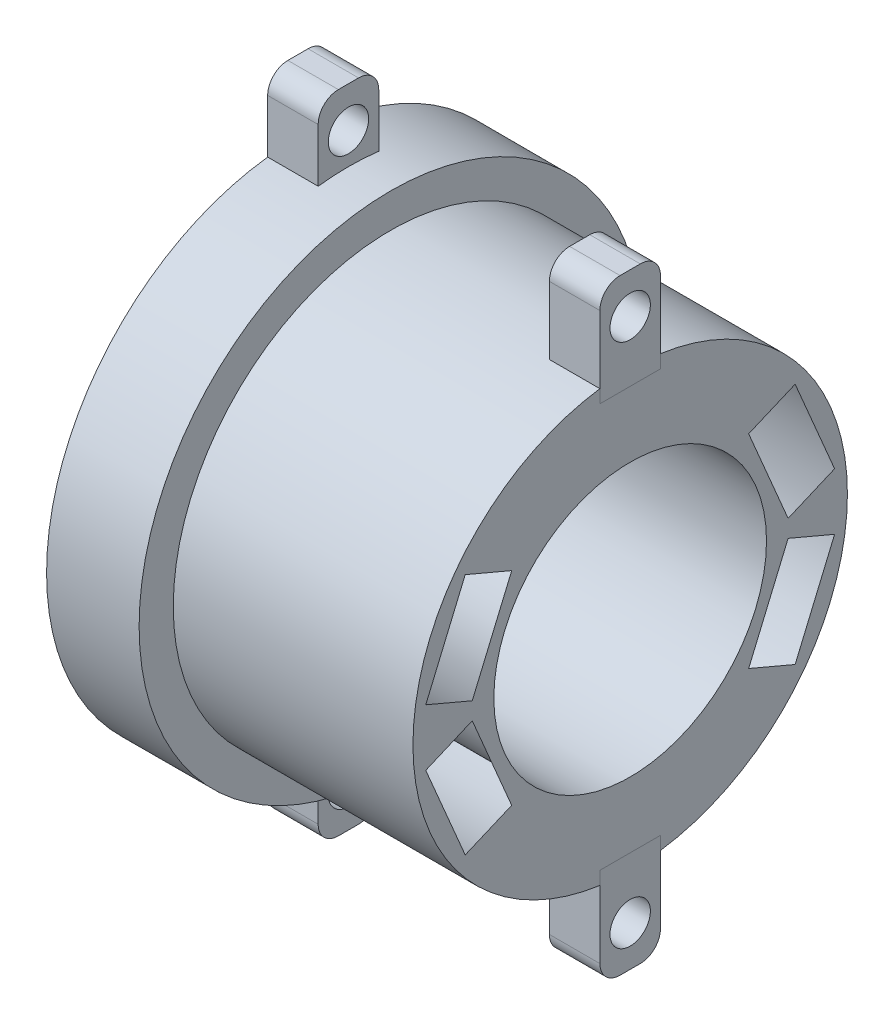
SolidWorks part; units mm, degrees
ref_plane "Front Plane" through (0, 0, 0) normal (0, 0, 1) x (1, 0, 0)
ref_plane "Top Plane" through (0, 0, 0) normal (0, 1, 0) x (1, 0, 0)
ref_plane "Right Plane" through (0, 0, 0) normal (1, 0, 0) x (0, 0, -1)
sketch "Sketch1" plane through (0, 0, 0) normal (0, 0, 1) x (1, 0, 0)
  line L1 (55, 0) -> (-55, 0) construction
  line L2 (-63.6748, 0) -> (-15.6177, 0)
  line L4 (-30.3791, 21.51) -> (-14.9144, 21.51)
  line L6 (-47.8088, 24.8909) -> (-47.8088, 22.9905)
  line L8 (-30.3744, 13.5) -> (-14.9144, 13.5)
  line L9 (-14.9144, 13.5) -> (-14.9144, 21.51)
  line L12 (-47.8088, 22.9905) -> (-40.2012, 23.0893)
  line L13 (-47.8088, 24.8909) -> (-38.6463, 24.8909)
  line L14 (-40.2012, 23.0893) -> (-40.3054, 13.5)
  line L15 (-40.3054, 13.5) -> (-30.3744, 13.5)
  line L17 (-38.6463, 24.8909) -> (-38.6463, 21.51)
  line L18 (-38.6463, 21.51) -> (-30.3791, 21.51)
  point P1 (-30.3791, 21.51)
  dimension "D1" = 21.51
  dimension "D4" = 13.5
revolve "Revolve-Thin12" add sketch "Sketch1" angle 360 about L2 wall 0.0001
sketch "Sketch2" plane through (-14.9143, 0, 0) normal (1, 0, 0) x (0, 0, -1)
  line L1 (-3, 30) -> (3, 30)
  line L2 (-3, 30) -> (-3, 20)
  line L3 (-3, 20) -> (3, 20)
  line L4 (3, 30) -> (3, 20)
  line L9 (-3, -30) -> (-3, -20)
  line L10 (3, -20) -> (-3, -20)
  line L11 (3, -30) -> (3, -20)
  line L12 (3, -30) -> (-3, -30)
  line L17 (-30, 3) -> (-20, 3) [skipped]
  line L18 (-20, -3) -> (-20, 3) [skipped]
  line L19 (-30, -3) -> (-20, -3) [skipped]
  line L20 (-30, -3) -> (-30, 3) [skipped]
  line L21 (30, -3) -> (20, -3) [skipped]
  line L22 (20, 3) -> (20, -3) [skipped]
  line L23 (30, 3) -> (20, 3) [skipped]
  line L24 (30, 3) -> (30, -3) [skipped]
  circle A0 centre (0, 26) radius 2
  circle A2 centre (0, -26) radius 2
  circle A5 centre (-26, 0) radius 2 [skipped]
  circle A6 centre (26, 0) radius 2 [skipped]
  point P4 (0, 30)
  point P29 (0, 0)
  dimension "D4" = 6
  dimension "D2" = 10
  dimension "D3" = 6
  dimension "D5" = 4
extrude "Boss-Extrude4" add sketch "Sketch2" along normal blind 0.0001 and the other way blind 5
fillet "Fillet2" radius 2 2 edges at (-17.4143, 30, -3) (-17.4143, 30, 3)
fillet "Fillet3" radius 2 2 edges at (-17.4143, -30, -3) (-17.4143, -30, 3)
sketch "Sketch3" plane through (-47.8089, 0, 0) normal (-1, 0, 0) x (0, 0, 1)
  line L1 (-3, 24) -> (3, 24)
  line L2 (-3, 24) -> (-3, 32)
  line L3 (-3, 32) -> (3, 32)
  line L4 (3, 24) -> (3, 32)
  circle A0 centre (0, 28) radius 2
  point P4 (0, 32)
  point P29 (-1, 0)
  dimension "D3" = 4
  dimension "D1" = 24
  dimension "D2" = 8
extrude "Boss-Extrude6" add sketch "Sketch3" along normal blind 0.0001 and the other way blind 5
mirror "Mirror7" about plane through (0, 0, 0) normal (0, 1, 0) of "Boss-Extrude6"
fillet "Fillet5" radius 2 2 edges at (-45.3089, 32, 3) (-45.3089, 32, -3)
fillet "Fillet6" radius 2 2 edges at (-45.3089, -32, 3) (-45.3089, -32, -3)
sketch "Sketch4" plane through (-14.9143, 0, 0) normal (1, 0, 0) x (0, 0, -1)
  line L0 (13.6845, 5.46) -> (18.287, 7.4137)
  line L1 (16.3333, 12.0162) -> (11.7308, 10.0625)
  line L2 (16.3333, 12.0162) -> (20.2406, 2.8111)
  line L3 (20.2406, 2.8111) -> (15.6381, 0.8575)
  line L4 (11.7308, 10.0625) -> (15.6381, 0.8575)
  point P2 (13.6845, 5.46)
  point P6 (18.287, 7.4137)
  dimension "D1" = 5.46
  dimension "D2" = 14.73
extrude "Cut-Extrude1" cut sketch "Sketch4" against normal offset from surface (23.3174 mm away) 2 contours L1 L4 L0 L2 | L0 L4 L3 L2 region at (-14.9143, 8.7381, -15.0089) region at (-14.9143, 4.1356, -16.9625) up to face at (-40.3055, 0, 13.4999)
mirror "Mirror8" about plane through (0, 0, 0) normal (0, 1, 0) of "Cut-Extrude1"
mirror "Mirror9" about plane through (0, 0, 0) normal (0, 0, 1) of "Mirror8"
